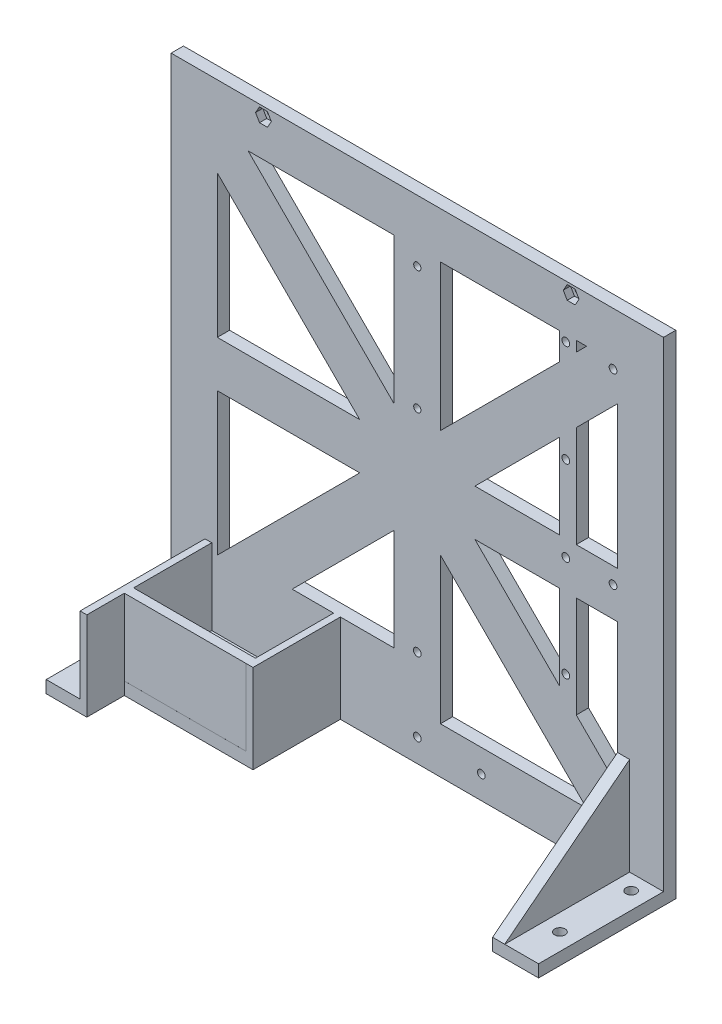
SolidWorks part; units mm, degrees
ref_plane "Front" through (0, 0, 0) normal (0, 0, 1) x (1, 0, 0)
ref_plane "Top" through (0, 0, 0) normal (0, 1, 0) x (1, 0, 0)
ref_plane "Right" through (0, 0, 0) normal (1, 0, 0) x (0, 0, -1)
sketch "Sketch1" plane through (0, 0, 0) normal (0, 0, 1) x (1, 0, 0)
  line L1 (-101.6, 101.6) -> (101.6, 101.6)
  line L2 (-101.6, 101.6) -> (-101.6, -101.6)
  line L3 (-101.6, -101.6) -> (101.6, -101.6)
  line L4 (101.6, 101.6) -> (101.6, -101.6)
  line L5 (-101.6, 101.6) -> (101.6, -101.6) construction
  line L6 (-101.6, -101.6) -> (101.6, 101.6) construction
  line L7 (0, -55) -> (0, 55) construction
  line L10 (-9.525, -22.8914) -> (-9.525, -65.024)
  line L17 (9.525, 22.225) -> (69.85, 82.55)
  line L18 (9.525, 82.55) -> (9.525, 22.225)
  line L19 (69.85, 82.55) -> (9.525, 82.55)
  line L23 (23.7658, 9.525) -> (82.55, 9.525)
  line L24 (23.7658, -9.525) -> (82.55, -9.525)
  line L25 (23.7658, 9.525) -> (82.55, 68.3092)
  line L26 (23.7658, -9.525) -> (82.55, -68.3092)
  line L27 (82.55, 9.525) -> (82.55, 68.3092)
  line L28 (82.55, -9.525) -> (82.55, -68.3092)
  line L29 (9.525, -22.225) -> (69.85, -82.55)
  line L30 (69.85, -82.55) -> (9.525, -82.55)
  line L31 (9.525, -82.55) -> (9.525, -22.225)
  line L32 (0, -101.6) -> (0, 101.6) construction
  line L36 (-82.55, -9.525) -> (-82.55, -68.3092)
  line L37 (-82.55, 9.525) -> (-82.55, 68.3092)
  line L38 (-23.7658, -9.525) -> (-82.55, -68.3092)
  line L39 (-23.7658, 9.525) -> (-82.55, 68.3092)
  line L40 (-23.7658, -9.525) -> (-82.55, -9.525)
  line L41 (-23.7658, 9.525) -> (-82.55, 9.525)
  line L42 (-69.85, 82.55) -> (-9.525, 82.55)
  line L43 (-9.525, 82.55) -> (-9.525, 22.225)
  line L44 (-9.525, 22.225) -> (-69.85, 82.55)
  line L45 (-9.525, -65.024) -> (-51.6576, -65.024)
  line L46 (-51.6576, -65.024) -> (-9.525, -22.8914)
  line L48 (58.7581, 87.2082) -> (65.6057, 87.2082)
  line L49 (58.7581, 87.2082) -> (58.7581, 4.2426)
  line L50 (58.7581, 4.2426) -> (65.6057, 4.2426)
  line L51 (65.6057, 87.2082) -> (65.6057, 4.2426)
  line L56 (58.7581, -5.8139) -> (65.6057, -5.8139)
  line L57 (58.7581, -5.8139) -> (58.7581, -58.6102)
  line L58 (58.7581, -58.6102) -> (65.6057, -58.6102)
  line L59 (65.6057, -5.8139) -> (65.6057, -58.6102)
  line L70 (90.1937, 58.9244) -> (90.1937, 51.0678)
  line L72 (0, 58.9244) -> (0, 51.0678)
  circle A0 centre (0, 76.2) radius 1.5
  circle A2 centre (0, 25.4) radius 1.5
  circle A3 centre (-63.5, 97.79) radius 1.5
  circle A4 centre (63.5, 97.79) radius 1.5
  point P0 (0, 0)
  dimension "D3" = 3
  dimension "D4" = 50.8
  dimension "D6" = 19.05
  dimension "D7" = 3
  dimension "D9" = 63.5
  dimension "D1" = 203.2
  dimension "D2" = 203.2
  dimension "D5" = 25.4
  dimension "D8" = 3.81
  dimension "D10" = 19.05
  dimension "D11" = 19.05
  dimension "D12" = 19.05
  dimension "D13" = 19.05
  dimension "D14" = 19.05
  dimension "D15" = 9.525
  dimension "D16" = 36.576
  dimension "D17" = 31.75
extrude "Boss-Extrude1" add sketch "Sketch1" along normal blind 5.08 contours L4 L1 L2 L3 L27 L23 L51 L50 L49 L25 L17 L18 L19 L48 L56 L59 L24 L28 L26 L58 L57 L45 L46 L10 L43 | L49 L48 L51 L50 | L57 L56 L59 L58 region at (-1.9817, -2.9175, 0)
sketch "Sketch2" plane through (0, 0, 5.08) normal (0, 0, 1) x (1, 0, 0)
  line L0 (-101.6, -101.6) -> (101.6, -101.6) construction
  line L2 (-101.6, -101.6) -> (-101.6, -96.52)
  line L5 (-9.525, -65.024) -> (-51.6576, -65.024) construction
  line L13 (-101.6, -101.6) -> (-31.75, -101.6)
  line L17 (-87.63, -65.024) -> (-84.836, -65.024)
  line L18 (-84.836, -96.4094) -> (-84.836, -65.024)
  line L23 (-84.836, -96.4094) -> (-34.544, -96.4094)
  line L24 (-101.6, -96.52) -> (-87.63, -96.52)
  line L25 (-87.63, -96.52) -> (-87.63, -65.024)
  line L28 (-34.544, -96.4094) -> (-34.544, -65.024)
  line L29 (-34.544, -65.024) -> (-31.75, -65.024)
  line L30 (-31.75, -65.024) -> (-31.75, -101.6)
  line L31 (101.6, -101.6) -> (87.63, -101.6)
  line L32 (101.6, -101.6) -> (101.6, -96.52)
  line L33 (101.6, -96.52) -> (87.63, -96.52)
  line L34 (87.63, -101.6) -> (87.63, -96.52)
  line M7 (101.6, -101.6) -> (101.6, 101.6)
  line M9 (-101.6, 101.6) -> (-101.6, -101.6)
  line M10 (-101.6, -101.6) -> (101.6, -101.6)
  dimension "D1" = 5.08
  dimension "D2" = 50.292
  dimension "D4" = 13.97
  dimension "D5" = 2.794
  dimension "D6" = 2.794
  dimension "D8" = 31.3854
extrude "Boss-Extrude2" add sketch "Sketch2" along normal blind 51.562 contours L23 L18 L17 L25 L24 M10 M9 | L34 L33 M10 M7 region at (94.615, -99.06, 5.08) region at (-100.8115, -99.06, 5.08)
sketch "Sketch3" plane through (0, -96.52, 0) normal (0, 1, 0) x (1, 0, 0)
  line L0 (-101.6, 0) -> (101.6, 0) construction
  line L2 (-87.63, -56.642) -> (-87.63, -5.08) construction
  line L4 (0, -55) -> (0, 55) construction
  line L5 (-101.6, -56.642) -> (-101.6, -5.08) construction
  circle A0 centre (-94.615, -11.43) radius 2.159
  circle A1 centre (94.615, -11.43) radius 2.159
  circle A2 centre (-94.615, -40.84) radius 2.159
  circle A3 centre (94.615, -40.84) radius 2.159
  dimension "D1" = 4.318
  dimension "D4" = 29.41
  dimension "D5" = 4.318
  dimension "D6" = 4.318
  dimension "D7" = 6.985
  dimension "D2" = 11.43
  dimension "D8" = 29.41
  dimension "D3" = 6.985
extrude "Cut-Extrude1" cut sketch "Sketch3" against normal up to next contours A0 | A1 | A3 | A2 | A2 | A3 region at (-94.615, -96.52, 11.43) region at (94.615, -96.52, 11.43) region at (-94.615, -96.52, 40.84) region at (94.615, -96.52, 40.84)
sketch "Sketch7" plane through (0, 0, 5.08) normal (0, 0, 1) x (1, 0, 0)
  line L1 (69.85, -82.55) -> (9.525, -82.55) construction
  circle A0 centre (0, -92.075) radius 1.5875
  circle A1 centre (0, -61.722) radius 1.5875
  circle A3 centre (26.416, -92.075) radius 1.5875
  dimension "D1" = 3.175
  dimension "D3" = 26.416
  dimension "D5" = 9.525
extrude "Cut-Extrude2" cut sketch "Sketch7" against normal up to next
sketch "Sketch11" plane through (0, 0, 5.08) normal (0, 0, 1) x (1, 0, 0)
  line L0 (0, -55) -> (0, 55) construction
  line L1 (-61.869, 94.965) -> (-60.238, 97.79)
  line L2 (-60.238, 97.79) -> (-61.869, 100.615)
  line L3 (-61.869, 100.615) -> (-65.131, 100.615)
  line L4 (-65.131, 100.615) -> (-66.762, 97.79)
  line L5 (-66.762, 97.79) -> (-65.131, 94.965)
  line L6 (-65.131, 94.965) -> (-61.869, 94.965)
  line L7 (65.131, 94.965) -> (61.869, 94.965)
  line L8 (66.762, 97.79) -> (65.131, 94.965)
  line L9 (65.131, 100.615) -> (66.762, 97.79)
  line L10 (61.869, 100.615) -> (65.131, 100.615)
  line L11 (60.238, 97.79) -> (61.869, 100.615)
  line L12 (61.869, 94.965) -> (60.238, 97.79)
  circle A0 centre (-63.5, 97.79) radius 1.5 construction
  circle A1 centre (-63.5, 97.79) radius 1.5
  circle A2 centre (-63.5, 97.79) radius 2.825 construction
  circle A3 centre (63.5, 97.79) radius 2.825 construction
  circle A4 centre (63.5, 97.79) radius 1.5
  dimension "D1" = 5.65
extrude "Cut-Extrude4" cut sketch "Sketch11" against normal blind 3 contours L5 L6 L1 L2 L3 L4 | L12 L7 L8 L9 L10 L11 region at (-63.5, 95.0513, 5.08) region at (63.5, 95.0513, 5.08)
sketch "Sketch12" plane through (-34.544, 0, 0) normal (-1, 0, 0) x (0, 0, 1)
  line L0 (56.642, -96.52) -> (5.08, -96.52) construction
  line L1 (41.148, -96.52) -> (37.338, -96.52)
  line L2 (41.148, -96.52) -> (41.148, -65.024)
  line L3 (41.148, -65.024) -> (37.338, -65.024)
  line L4 (37.338, -96.52) -> (37.338, -65.024)
  line L5 (56.642, -65.024) -> (5.08, -65.024) construction
  line L6 (5.08, 101.6) -> (5.08, -96.52) construction
  dimension "D1" = 3.81
  dimension "D2" = 32.258
extrude "Boss-Extrude3" add sketch "Sketch12" along normal up to next
sketch "Sketch14" plane through (-31.75, 0, 0) normal (1, 0, 0) x (0, 0, -1)
  line L0 (-56.642, -65.024) -> (-5.08, -65.024) construction
  line L1 (-56.642, -101.6) -> (-41.152, -101.6)
  line L2 (-56.642, -101.6) -> (-56.642, -65.024)
  line L3 (-56.642, -65.024) -> (-41.152, -65.024)
  line L4 (-41.152, -101.6) -> (-41.152, -65.024)
  dimension "D1" = 15.49
extrude "Cut-Extrude5" cut sketch "Sketch14" against normal up to surface (53.086 mm away) up to face at (-84.836, -80.7167, 48.895)
sketch "Sketch15" plane through (0, 0, 5.08) normal (0, 0, 1) x (1, 0, 0)
  line L0 (61.2852, -38.9377) -> (80.7852, -38.9377) construction
  line L1 (61.2852, 37.854) -> (80.7852, 37.854) construction
  line L2 (61.2852, 37.854) -> (61.2852, 79.854) construction
  line L3 (61.2852, 79.854) -> (80.7852, 79.854) construction
  line L4 (80.7852, 37.854) -> (80.7852, 79.854) construction
  line L5 (61.2852, -38.9377) -> (61.2852, 2.7864) construction
  line L6 (61.2852, 2.7864) -> (80.7852, 2.7864) construction
  line L7 (80.7852, -38.9377) -> (80.7852, 2.7864) construction
  circle A0 centre (61.2852, 79.854) radius 1.6
  circle A1 centre (80.7852, 79.854) radius 1.6
  circle A2 centre (80.7852, 37.854) radius 1.6
  circle A3 centre (61.2852, 37.854) radius 1.6
  circle A4 centre (61.2852, 2.7864) radius 1.6
  circle A5 centre (80.7852, 2.7864) radius 1.6
  circle A6 centre (80.7852, -38.9377) radius 1.6
  circle A7 centre (61.2852, -38.9377) radius 1.6
  dimension "D1" = 19.5
  dimension "D2" = 42
  dimension "D3" = 3.2
  dimension "D4" = 3.2
  dimension "D5" = 3.2
  dimension "D6" = 3.2
  dimension "D8" = 3.2
  dimension "D9" = 3.2
  dimension "D10" = 3.2
  dimension "D7" = 19.5
  dimension "D11" = 41.7241
extrude "Cut-Extrude6" cut sketch "Sketch15" against normal blind 10
sketch "Sketch16" plane through (0, 0, 0) normal (0, 0, -1) x (-1, 0, 0)
  line L1 (-1.5877, 73.45) -> (1.5877, 73.45)
  line L2 (1.5877, 73.45) -> (3.1754, 76.2)
  line L3 (3.1754, 76.2) -> (1.5877, 78.95)
  line L4 (1.5877, 78.95) -> (-1.5877, 78.95)
  line L5 (-1.5877, 78.95) -> (-3.1754, 76.2)
  line L6 (-3.1754, 76.2) -> (-1.5877, 73.45)
  line L7 (-62.8729, 77.104) -> (-59.6975, 77.104)
  line L8 (-59.6975, 77.104) -> (-58.1097, 79.854)
  line L9 (-58.1097, 79.854) -> (-59.6975, 82.604)
  line L10 (-59.6975, 82.604) -> (-62.8729, 82.604)
  line L11 (-62.8729, 82.604) -> (-64.4606, 79.854)
  line L12 (-64.4606, 79.854) -> (-62.8729, 77.104)
  line L13 (-82.3729, 77.104) -> (-79.1975, 77.104)
  line L14 (-79.1975, 77.104) -> (-77.6097, 79.854)
  line L15 (-77.6097, 79.854) -> (-79.1975, 82.604)
  line L16 (-79.1975, 82.604) -> (-82.3729, 82.604)
  line L17 (-82.3729, 82.604) -> (-83.9606, 79.854)
  line L18 (-83.9606, 79.854) -> (-82.3729, 77.104)
  line L19 (-62.8729, 35.104) -> (-59.6975, 35.104)
  line L20 (-59.6975, 35.104) -> (-58.1097, 37.854)
  line L21 (-58.1097, 37.854) -> (-59.6975, 40.604)
  line L22 (-59.6975, 40.604) -> (-62.8729, 40.604)
  line L23 (-62.8729, 40.604) -> (-64.4606, 37.854)
  line L24 (-64.4606, 37.854) -> (-62.8729, 35.104)
  line L25 (-3.1754, 25.4) -> (-1.5877, 22.65)
  line L26 (-1.5877, 22.65) -> (1.5877, 22.65)
  line L27 (1.5877, 22.65) -> (3.1754, 25.4)
  line L28 (3.1754, 25.4) -> (1.5877, 28.15)
  line L29 (1.5877, 28.15) -> (-1.5877, 28.15)
  line L30 (-1.5877, 28.15) -> (-3.1754, 25.4)
  line L31 (-64.4606, 2.7864) -> (-62.8729, 0.0364)
  line L32 (-62.8729, 0.0364) -> (-59.6975, 0.0364)
  line L33 (-59.6975, 0.0364) -> (-58.1097, 2.7864)
  line L34 (-58.1097, 2.7864) -> (-59.6975, 5.5364)
  line L35 (-59.6975, 5.5364) -> (-62.8729, 5.5364)
  line L36 (-62.8729, 5.5364) -> (-64.4606, 2.7864)
  line L37 (-83.9606, 2.7864) -> (-82.3729, 0.0364)
  line L38 (-82.3729, 0.0364) -> (-79.1975, 0.0364)
  line L39 (-79.1975, 0.0364) -> (-77.6097, 2.7864)
  line L40 (-77.6097, 2.7864) -> (-79.1975, 5.5364)
  line L41 (-79.1975, 5.5364) -> (-82.3729, 5.5364)
  line L42 (-82.3729, 5.5364) -> (-83.9606, 2.7864)
  line L43 (-64.4606, -38.9377) -> (-62.8729, -41.6877)
  line L44 (-62.8729, -41.6877) -> (-59.6975, -41.6877)
  line L45 (-59.6975, -41.6877) -> (-58.1097, -38.9377)
  line L46 (-58.1097, -38.9377) -> (-59.6975, -36.1877)
  line L47 (-59.6975, -36.1877) -> (-62.8729, -36.1877)
  line L48 (-62.8729, -36.1877) -> (-64.4606, -38.9377)
  line L49 (-3.1754, -61.722) -> (-1.5877, -64.472)
  line L50 (-1.5877, -64.472) -> (1.5877, -64.472)
  line L51 (1.5877, -64.472) -> (3.1754, -61.722)
  line L52 (3.1754, -61.722) -> (1.5877, -58.972)
  line L53 (1.5877, -58.972) -> (-1.5877, -58.972)
  line L54 (-1.5877, -58.972) -> (-3.1754, -61.722)
  line L55 (-3.1754, -92.075) -> (-1.5877, -94.825)
  line L56 (-1.5877, -94.825) -> (1.5877, -94.825)
  line L57 (1.5877, -94.825) -> (3.1754, -92.075)
  line L58 (3.1754, -92.075) -> (1.5877, -89.325)
  line L59 (1.5877, -89.325) -> (-1.5877, -89.325)
  line L60 (-1.5877, -89.325) -> (-3.1754, -92.075)
  line L61 (-29.5914, -92.075) -> (-28.0037, -94.825)
  line L62 (-28.0037, -94.825) -> (-24.8283, -94.825)
  line L63 (-24.8283, -94.825) -> (-23.2406, -92.075)
  line L64 (-23.2406, -92.075) -> (-24.8283, -89.325)
  line L65 (-24.8283, -89.325) -> (-28.0037, -89.325)
  line L66 (-28.0037, -89.325) -> (-29.5914, -92.075)
  circle A0 centre (0, 76.2) radius 2.75 construction
  circle A1 centre (-61.2852, 79.854) radius 2.75 construction
  circle A2 centre (-80.7852, 79.854) radius 2.75 construction
  circle A3 centre (-61.2852, 37.854) radius 2.75 construction
  circle A4 centre (0, 25.4) radius 2.75 construction
  circle A5 centre (-61.2852, 2.7864) radius 2.75 construction
  circle A6 centre (-80.7852, 2.7864) radius 2.75 construction
  circle A7 centre (-61.2852, -38.9377) radius 2.75 construction
  circle A8 centre (0, -61.722) radius 2.75 construction
  circle A9 centre (0, -92.075) radius 2.75 construction
  circle A10 centre (-26.416, -92.075) radius 2.75 construction
  dimension "D1" = 5.5
  dimension "D2" = 5.5
extrude "Cut-Extrude7" cut sketch "Sketch16" against normal blind 2.3
sketch "Sketch17" plane through (101.6, 0, 0) normal (1, 0, 0) x (0, 0, -1)
  line L0 (-56.642, -96.52) -> (-5.08, -56.2524)
  line L1 (-5.08, 101.6) -> (-5.08, -96.52) construction
  line L2 (-5.08, -56.2524) -> (-5.08, -96.52)
  line L3 (-56.642, -101.6) -> (0, -101.6) construction
  line L4 (-5.08, -96.52) -> (-56.642, -96.52)
  line L5 (-56.642, -96.52) -> (-5.08, -96.52)
  line L6 (-56.642, -96.52) -> (-56.642, -101.6)
  line L7 (-56.642, -101.6) -> (-5.08, -101.6)
  line L8 (-5.08, -96.52) -> (-5.08, -101.6)
  line M6 (-5.08, 101.6) -> (-5.08, -96.52)
  line M7 (-5.08, -96.52) -> (-56.642, -96.52)
  line M8 (-56.642, -96.52) -> (-56.642, -101.6)
  line M9 (-56.642, -101.6) -> (0, -101.6)
extrude "Boss-Extrude5" add sketch "Sketch17" against normal blind 5 from surface contours L0 M7 M6 | L8 M7 M8 M9 region at (101.6, -83.0975, 22.2673) region at (101.6, -99.06, 30.861) starting at face at (87.63, -99.06, 30.861)
